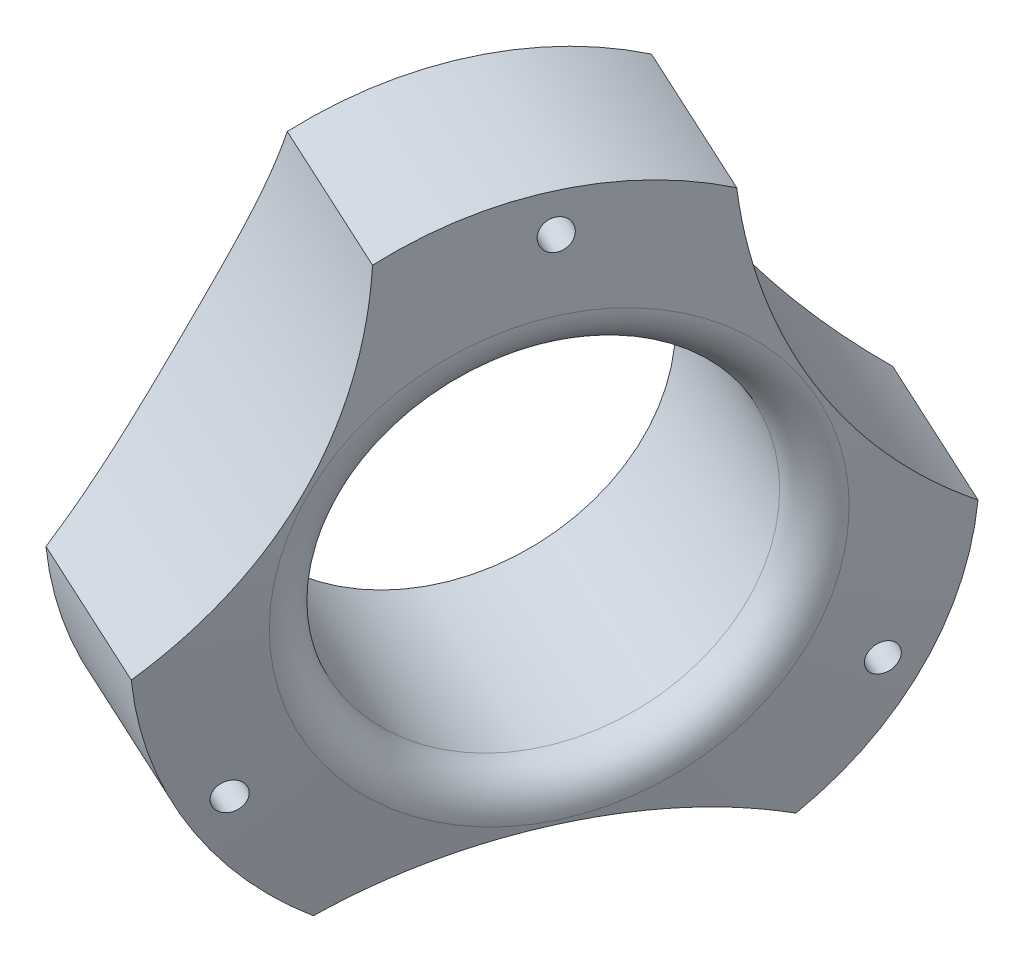
SolidWorks part; units mm, degrees
material "ABS"
ref_plane "前视基准面" through (0, 0, 0) normal (0, 0, 1) x (1, 0, 0)
ref_plane "上视基准面" through (0, 0, 0) normal (0, 1, 0) x (1, 0, 0)
ref_plane "右视基准面" through (0, 0, 0) normal (1, 0, 0) x (0, 0, -1)
other "Configuration Table"
sketch "草图1" plane through (0, 0, 0) normal (0, 1, 0) x (1, 0, 0)
  line L0 (0, 0) -> (50000, 0) construction
  line L1 (0, 0) -> (43301.2702, 25000) construction
  line L2 (0, 0) -> (25000, 43301.2702) construction
  line L3 (0, 0) -> (0, 50000) construction
  line L4 (0, 0) -> (-25000, 43301.2702) construction
  line L5 (0, 0) -> (-43301.2702, 25000) construction
  line L6 (11.039, 19.1201) -> (22.2401, 38.5209)
  line L7 (22.2401, 38.5209) -> (0, 48.7842)
  line L8 (0, 48.7842) -> (0, 24.2143)
  line L9 (0, 24.2143) -> (11.039, 19.1201)
  line L10 (13.3185, 42.638) -> (9.1284, 33.5582) construction
  line L11 (9.1284, 33.5582) -> (17.2192, 29.8245)
  line L12 (9.1284, 33.5582) -> (0, 37.7707)
  spline S0 degree 4 poles (4.5441, -13.9852) (5.069, -13.9115) (6.1117, -13.7144) (7.5966, -13.2868) (9.4525, -12.4738) (11.1485, -11.4611) (12.673, -10.2854) (14.0902, -8.9027) (15.2006, -7.528) (16.0517, -6.2294) (16.6357, -5.1571) (16.9969, -4.4036) (17.2795, -3.7437) (17.4701, -3.2541) (17.647, -2.7595) (17.7869, -2.3315) (17.8956, -1.9726) (17.9965, -1.6106) (18.0724, -1.3201) (18.1431, -1.0312) (18.201, -0.7763) (18.2495, -0.5466) (18.2961, -0.3139) (18.338, -0.0934) (18.3688, 0.0809) (18.404, 0.2961) (18.438, 0.517) (18.4698, 0.7375) (18.5019, 0.9839) (18.5336, 1.2626) (18.5616, 1.5443) (18.5855, 1.8273) (18.6051, 2.1103) (18.6204, 2.3933) (18.6344, 2.7473) (18.6427, 3.1726) (18.6402, 3.6687) (18.606, 4.6606) (18.4743, 6.0736) (18.1443, 7.891) (17.4882, 10.0676) (16.5951, 12.1579) (15.4804, 14.1385) (14.1536, 15.9992) (12.6297, 17.7192) (10.7951, 19.3989) (8.6272, 20.9716) (6.1287, 22.3558) (3.3088, 23.4722) (0.3713, 24.2251) (-2.6362, 24.611) (-5.6679, 24.6319) (-8.6804, 24.2953) (-11.6337, 23.6131) (-14.4905, 22.6011) (-17.8988, 20.9477) (-21.6682, 18.3857) (-25.4815, 14.66) (-28.8831, 9.6089) (-31.2279, 3.9916) (-32.5355, -2.3024) (-32.5832, -9.4982) (-30.886, -17.2942) (-27.0418, -25.1548) (-21.1423, -32.1629) (-13.78, -37.6027) (-5.394, -41.2569) (3.5764, -43.0207) (12.7127, -42.8868) (21.6333, -40.9289) (30.0036, -37.2857) (37.5425, -32.1439) (44.0239, -25.7248) (49.277, -18.2707) (53.1837, -10.0336) (55.6749, -1.2666) (56.7255, 7.7843) (56.3496, 16.8863) (54.5948, 25.8236) (51.5367, 34.4007) (47.2736, 42.4454) (41.6252, 50.2164) (33.2939, 58.6988) (21.6024, 66.7973) (6.2316, 72.9489) (-11.9297, 75.3897) (-30.1426, 73.5037) (-47.4501, 67.5662) (-63.0493, 58.0235) (-76.3038, 45.4399) (-86.7456, 30.4509) (-94.067, 13.7235) (-98.1075, -4.0757) (-98.837, -22.3066) (-96.337, -40.374) (-90.7813, -57.7411) (-82.4178, -73.9383) (-71.5503, -88.568) (-58.5225, -101.306) (-43.7037, -111.9004) (-27.476, -120.169) (-10.2235, -125.9948) (7.6766, -129.3207) (25.8616, -130.1437) (43.989, -128.5088) (59.522, -125.003) (72.4202, -120.5917) (82.8104, -116.0253) (90.8771, -111.8583) (98.6697, -107.1992) (106.1617, -102.071) (114.2246, -95.801) (122.6763, -88.2215) (131.2888, -79.1727) (139.0767, -69.4058) (144.8157, -60.9536) (149.48, -53.1674) (153.2371, -46.1706) (156.1751, -40.0285) (158.8259, -33.7588) (160.8418, -28.4575) (162.3378, -24.1741) (163.5443, -20.3917) (164.5049, -17.1274) (165.2564, -14.393) (165.828, -12.1982) (166.3703, -9.9944) (166.8184, -8.0627) (167.1848, -6.398) (167.4765, -5.0161) (167.7053, -3.8925) (167.892, -2.9476) (168.0629, -2.0497) (168.1956, -1.3461) (168.4043, -0.1916) (168.4882, 0.2863) (168.6688, 1.3366) (168.7622, 1.9047) (168.8711, 2.5704) (169.0198, 3.5044) (169.1948, 4.6573) (169.389, 6.0027) (169.5701, 7.3351) (169.7422, 8.6768) (169.9433, 10.3507) (170.1641, 12.3645) (170.391, 14.7154) (170.6086, 17.4069) (170.7844, 20.1009) (170.9186, 22.7976) (171.0111, 25.4959) (171.0621, 28.1953) (171.0718, 30.8952) (171.0401, 33.595) (170.9491, 36.9686) (170.6302, 43.7113) (169.6923, 53.7988) (167.722, 65.8035) (165.138, 76.2991) (163.208, 82.7681) (162.3863, 85.3399) knots 0 0 0 0 0 0.002183 0.004365 0.006343 0.00832 0.010298 0.012275 0.014479 0.01558 0.016682 0.0173 0.017918 0.018536 0.018845 0.019463 0.019772 0.020081 0.02039 0.020699 0.021008 0.021162 0.021317 0.021626 0.021918 0.022064 0.02221 0.022501 0.022793 0.023085 0.023377 0.023669 0.023961 0.024253 0.024544 0.025128 0.025712 0.026296 0.028631 0.030966 0.033302 0.035637 0.037972 0.040307 0.042695 0.045083 0.048197 0.05131 0.054424 0.057538 0.060652 0.063766 0.066879 0.069993 0.073107 0.07622 0.082448 0.088676 0.094903 0.10113 0.107357 0.114993 0.124334 0.133675 0.143016 0.152357 0.161699 0.17104 0.18038 0.189722 0.199063 0.208404 0.217745 0.227086 0.236427 0.245769 0.25511 0.264451 0.273792 0.283133 0.292474 0.301815 0.313225 0.331907 0.35059 0.369272 0.387954 0.406636 0.425318 0.444001 0.462683 0.481365 0.500047 0.518729 0.537412 0.556094 0.574776 0.593458 0.612141 0.630823 0.649505 0.668187 0.68687 0.705552 0.724234 0.742916 0.752258 0.761599 0.77094 0.780281 0.789622 0.798963 0.812975 0.826987 0.840998 0.85034 0.85501 0.864351 0.873692 0.878363 0.883033 0.887704 0.892374 0.89471 0.897045 0.89938 0.901716 0.904051 0.905219 0.906387 0.907554 0.908722 0.909306 0.90989 0.911057 0.912447 0.912794 0.913142 0.913837 0.915226 0.916616 0.918006 0.919396 0.920785 0.922175 0.924955 0.927734 0.930513 0.933293 0.936072 0.938852 0.941631 0.944411 0.94719 0.94997 0.955529 0.972205 0.988882 1 1 1 1 1 construction
  spline S1 degree 4 poles (18.3541, 0) (18.3651, 0.0621) (18.381, 0.1554) (18.404, 0.2961) (18.438, 0.517) (18.4698, 0.7375) (18.5019, 0.9839) (18.5336, 1.2626) (18.5616, 1.5443) (18.5855, 1.8273) (18.6051, 2.1103) (18.6204, 2.3933) (18.6344, 2.7473) (18.6427, 3.1726) (18.6402, 3.6687) (18.606, 4.6606) (18.4743, 6.0736) (18.1443, 7.891) (17.4882, 10.0676) (16.5951, 12.1579) (15.4804, 14.1385) (14.1536, 15.9992) (12.6297, 17.7192) (10.7951, 19.3989) (8.6272, 20.9716) (6.1287, 22.3558) (3.3088, 23.4722) (0.3713, 24.2251) (-2.6362, 24.611) (-5.6679, 24.6319) (-8.6804, 24.2953) (-11.6337, 23.6131) (-14.4905, 22.6011) (-17.8988, 20.9477) (-21.6682, 18.3857) (-25.4815, 14.66) (-28.8831, 9.6089) (-31.2279, 3.9916) (-32.5355, -2.3024) (-32.5832, -9.4982) (-30.886, -17.2942) (-27.0418, -25.1548) (-21.1423, -32.1629) (-13.78, -37.6027) (-5.394, -41.2569) (3.5764, -43.0207) (12.7127, -42.8868) (21.6333, -40.9289) (30.0036, -37.2857) (37.5425, -32.1439) (44.0239, -25.7248) (49.277, -18.2707) (53.1837, -10.0336) (55.6749, -1.2666) (56.7255, 7.7843) (56.3496, 16.8863) (54.5948, 25.8236) (51.5367, 34.4007) (47.2736, 42.4454) (41.6252, 50.2164) (33.2939, 58.6988) (21.6024, 66.7973) (6.2316, 72.9489) (-11.9297, 75.3897) (-30.1426, 73.5037) (-47.4501, 67.5662) (-63.0493, 58.0235) (-76.3038, 45.4399) (-86.7456, 30.4509) (-94.067, 13.7235) (-98.1075, -4.0757) (-98.837, -22.3066) (-96.337, -40.374) (-90.7813, -57.7411) (-82.4178, -73.9383) (-71.5503, -88.568) (-58.5225, -101.306) (-43.7037, -111.9004) (-27.476, -120.169) (-10.2235, -125.9948) (7.6766, -129.3207) (25.8616, -130.1437) (43.989, -128.5088) (59.522, -125.003) (72.4202, -120.5917) (82.8104, -116.0253) (90.8771, -111.8583) (98.6697, -107.1992) (106.1617, -102.071) (114.2246, -95.801) (122.6763, -88.2215) (131.2888, -79.1727) (139.0767, -69.4058) (144.8157, -60.9536) (149.48, -53.1674) (153.2371, -46.1706) (156.1751, -40.0285) (158.8259, -33.7588) (160.8418, -28.4575) (162.3378, -24.1741) (163.5443, -20.3917) (164.5049, -17.1274) (165.2564, -14.393) (165.828, -12.1982) (166.3703, -9.9944) (166.8184, -8.0627) (167.1848, -6.398) (167.4765, -5.0161) (167.7053, -3.8925) (167.892, -2.9476) (168.0629, -2.0497) (168.1956, -1.3461) (168.3264, -0.6223) (168.3933, -0.2484) (168.4372, 0) knots 0.021626 0.021626 0.021626 0.021626 0.021626 0.021918 0.022064 0.02221 0.022501 0.022793 0.023085 0.023377 0.023669 0.023961 0.024253 0.024544 0.025128 0.025712 0.026296 0.028631 0.030966 0.033302 0.035637 0.037972 0.040307 0.042695 0.045083 0.048197 0.05131 0.054424 0.057538 0.060652 0.063766 0.066879 0.069993 0.073107 0.07622 0.082448 0.088676 0.094903 0.10113 0.107357 0.114993 0.124334 0.133675 0.143016 0.152357 0.161699 0.17104 0.18038 0.189722 0.199063 0.208404 0.217745 0.227086 0.236427 0.245769 0.25511 0.264451 0.273792 0.283133 0.292474 0.301815 0.313225 0.331907 0.35059 0.369272 0.387954 0.406636 0.425318 0.444001 0.462683 0.481365 0.500047 0.518729 0.537412 0.556094 0.574776 0.593458 0.612141 0.630823 0.649505 0.668187 0.68687 0.705552 0.724234 0.742916 0.752258 0.761599 0.77094 0.780281 0.789622 0.798963 0.812975 0.826987 0.840998 0.85034 0.85501 0.864351 0.873692 0.878363 0.883033 0.887704 0.892374 0.89471 0.897045 0.89938 0.901716 0.904051 0.905219 0.906387 0.907554 0.908722 0.909306 0.90989 0.911057 0.911057 0.911057 0.911057 0.911057
  spline S2 degree 4 poles (26.7771, -19.4547) (27.2791, -18.9699) (28.2564, -17.9726) (29.6389, -16.3972) (31.5138, -13.8737) (32.9647, -11.4834) (34.0651, -9.2997) (34.8847, -7.3726) (35.3191, -6.2309) (35.6599, -5.2409) (35.9229, -4.4091) (36.0959, -3.8235) (36.2363, -3.3192) (36.3702, -2.8132) (36.4765, -2.3905) (36.5777, -1.9654) (36.6735, -1.5395) (36.7371, -1.2443) (36.7899, -0.9895) (36.8338, -0.7701) (36.8689, -0.5895) (36.9122, -0.3614) (36.9643, -0.079) (37.0022, 0.137) (37.056, 0.4587) (37.1012, 0.7414) (37.1347, 0.96) (37.1737, 1.2255) (37.2176, 1.5413) (37.2661, 1.9157) (37.3168, 2.3441) (37.3624, 2.7721) (37.4134, 3.3079) (37.4649, 3.9519) (37.524, 4.9191) (37.5642, 6.2107) (37.5499, 8.58) (37.2749, 12.0191) (36.4953, 16.2666) (34.9181, 21.2024) (32.7382, 25.9024) (30.2297, 29.9345) (27.5748, 33.3344) (24.3272, 36.7897) (20.4102, 40.1789) (15.3713, 43.5302) (9.113, 46.471) (2.4988, 48.4837) (-3.4771, 49.4179) (-8.6498, 49.6296) (-15.5372, 49.2939) (-22.3494, 48.0444) (-29.7217, 45.4984) (-37.3047, 41.3681) (-42.9225, 37.3494) (-49.2948, 31.5248) (-55.7813, 23.4083) (-61.4472, 12.6507) (-65.4181, -1.9048) (-66.0143, -20.496) (-61.2011, -38.6277) (-51.6663, -54.6681) (-39.5267, -67.0168) (-28.241, -75.0457) (-15.7631, -81.0448) (-2.4709, -84.9081) (11.2641, -86.5959) (25.0917, -86.1269) (38.6859, -83.5703) (51.7521, -79.0376) (62.4941, -73.4702) (71.0671, -67.6624) (77.7289, -62.1925) (82.7475, -57.4634) (87.4361, -52.4071) (91.7776, -47.05) (95.7571, -41.4188) (99.3618, -35.5409) (102.1786, -30.2056) (104.3465, -25.5122) (105.8226, -21.9278) (106.7439, -19.5134) (107.4694, -17.486) (108.0246, -15.8552) (108.5543, -14.216) (109.0585, -12.5687) (109.5372, -10.914) (109.9904, -9.2519) (110.418, -7.5833) (110.7697, -6.1172) (111.0551, -4.8577) (111.2824, -3.8044) (111.4574, -2.9629) (111.6056, -2.2213) (111.7181, -1.6396) (111.7961, -1.2276) (111.8764, -0.7956) (111.9824, -0.2107) (112.0406, 0.1173) (112.149, 0.7476) (112.2197, 1.1704) (112.2736, 1.499) (112.3401, 1.912) (112.4454, 2.5814) (112.5829, 3.4978) (112.7468, 4.6683) (112.9181, 6.007) (113.1127, 7.6834) (113.3147, 9.6981) (113.5046, 12.0531) (113.6588, 14.7487) (113.7504, 17.4473) (113.7796, 20.1472) (113.7303, 24.197) (113.4243, 30.2662) (112.8255, 35.6383) (112.057, 40.3021) (111.5392, 42.9519) knots 0 0 0 0 0 0.005611 0.011222 0.016833 0.02525 0.028055 0.030861 0.033666 0.035069 0.036472 0.037875 0.038576 0.039277 0.04068 0.041381 0.042083 0.042784 0.043135 0.043486 0.043836 0.044187 0.044888 0.045754 0.046187 0.04662 0.047052 0.047485 0.048351 0.049216 0.050082 0.050948 0.051813 0.053545 0.055276 0.058738 0.062201 0.072588 0.082976 0.093363 0.103751 0.114138 0.121063 0.127988 0.141838 0.155688 0.169538 0.183388 0.197238 0.204163 0.211088 0.238788 0.252638 0.266488 0.280339 0.294189 0.321888 0.349589 0.377289 0.414571 0.469971 0.497671 0.525371 0.553071 0.580771 0.608471 0.636171 0.663871 0.691571 0.719271 0.746971 0.760821 0.774671 0.788521 0.802371 0.816222 0.830072 0.843922 0.857772 0.864697 0.871622 0.875084 0.878547 0.882009 0.885472 0.888934 0.892397 0.895859 0.899322 0.902784 0.904515 0.906247 0.907978 0.909709 0.910575 0.911008 0.91144 0.913172 0.914528 0.915207 0.915885 0.916563 0.917242 0.918599 0.921312 0.924025 0.926739 0.929452 0.934879 0.940306 0.945732 0.951159 0.956586 0.962013 0.978293 1 1 1 1 1 construction
  spline S3 degree 4 poles (36.9778, 0) (36.994, 0.0921) (37.0177, 0.2297) (37.056, 0.4587) (37.1012, 0.7414) (37.1347, 0.96) (37.1737, 1.2255) (37.2176, 1.5413) (37.2661, 1.9157) (37.3168, 2.3441) (37.3624, 2.7721) (37.4134, 3.3079) (37.4649, 3.9519) (37.524, 4.9191) (37.5642, 6.2107) (37.5499, 8.58) (37.2749, 12.0191) (36.4953, 16.2666) (34.9181, 21.2024) (32.7382, 25.9024) (30.2297, 29.9345) (27.5748, 33.3344) (24.3272, 36.7897) (20.4102, 40.1789) (15.3713, 43.5302) (9.113, 46.471) (2.4988, 48.4837) (-3.4771, 49.4179) (-8.6498, 49.6296) (-15.5372, 49.2939) (-22.3494, 48.0444) (-29.7217, 45.4984) (-37.3047, 41.3681) (-42.9225, 37.3494) (-49.2948, 31.5248) (-55.7813, 23.4083) (-61.4472, 12.6507) (-65.4181, -1.9048) (-66.0143, -20.496) (-61.2011, -38.6277) (-51.6663, -54.6681) (-39.5267, -67.0168) (-28.241, -75.0457) (-15.7631, -81.0448) (-2.4709, -84.9081) (11.2641, -86.5959) (25.0917, -86.1269) (38.6859, -83.5703) (51.7521, -79.0376) (62.4941, -73.4702) (71.0671, -67.6624) (77.7289, -62.1925) (82.7475, -57.4634) (87.4361, -52.4071) (91.7776, -47.05) (95.7571, -41.4188) (99.3618, -35.5409) (102.1786, -30.2056) (104.3465, -25.5122) (105.8226, -21.9278) (106.7439, -19.5134) (107.4694, -17.486) (108.0246, -15.8552) (108.5543, -14.216) (109.0585, -12.5687) (109.5372, -10.914) (109.9904, -9.2519) (110.418, -7.5833) (110.7697, -6.1172) (111.0551, -4.8577) (111.2824, -3.8044) (111.4574, -2.9629) (111.6056, -2.2213) (111.7181, -1.6396) (111.7961, -1.2276) (111.8764, -0.7956) (111.946, -0.4114) (111.9868, -0.1841) (112.0193, 0) knots 0.044888 0.044888 0.044888 0.044888 0.044888 0.045754 0.046187 0.04662 0.047052 0.047485 0.048351 0.049216 0.050082 0.050948 0.051813 0.053545 0.055276 0.058738 0.062201 0.072588 0.082976 0.093363 0.103751 0.114138 0.121063 0.127988 0.141838 0.155688 0.169538 0.183388 0.197238 0.204163 0.211088 0.238788 0.252638 0.266488 0.280339 0.294189 0.321888 0.349589 0.377289 0.414571 0.469971 0.497671 0.525371 0.553071 0.580771 0.608471 0.636171 0.663871 0.691571 0.719271 0.746971 0.760821 0.774671 0.788521 0.802371 0.816222 0.830072 0.843922 0.857772 0.864697 0.871622 0.875084 0.878547 0.882009 0.885472 0.888934 0.892397 0.895859 0.899322 0.902784 0.904515 0.906247 0.907978 0.909709 0.910575 0.911008 0.91144 0.913172 0.913172 0.913172 0.913172 0.913172
  point P28 (9.1284, 33.5582)
  dimension "D1" = 10
revolve "旋转1" add sketch "草图1" angle 360 about L7 region at (7.2301, 0, -28.3935) region at (5.6712, 0, -21.9501)
ref_plane "基准面1" through (2.8492, 0, 1.3148) normal (0.908, 0, 0.419) x (0.419, 0, -0.908)
sketch "草图2" plane through (2.8492, 0, 1.3148) normal (0.908, 0, 0.419) x (0.419, 0, -0.908)
  line L0 (44.2951, 22.309) -> (44.2951, 19.809) construction
  line L1 (44.2951, 0) -> (13.9392, 0) construction
  line L2 (44.2951, 0) -> (5.324, 22.5) construction
  circle A0 centre (44.2951, 0) radius 22.309 construction
  circle A1 centre (44.2951, 19.809) radius 1
  circle A2 centre (5.324, 22.5) radius 29.5
  circle A3 centre (83.2663, 22.5) radius 29.5
  circle A4 centre (61.4502, -9.9045) radius 1
  circle A5 centre (44.2951, -45) radius 29.5
  circle A6 centre (27.14, -9.9045) radius 1
  circle A7 centre (44.2951, 0) radius 12.5
  dimension "D2" = 2
  dimension "D4" = 59
  dimension "D6" = 25
  dimension "D1" = 2.5
  dimension "D3" = 30
  dimension "D5" = 3
extrude "切除-拉伸1" cut sketch "草图2" against normal blind 24 contours A2 | A3 | A5 | A1 | A6 | A4 | A7 region at (21.4093, 19.809, -38.9043) region at (5.08, 22.5, -3.5192) region at (37.7386, 22.5, -74.2894) region at (28.5974, -9.9045, -54.4808) region at (21.4093, -45, -38.9043) region at (14.2211, -9.9045, -23.3278) region at (21.4093, 0, -38.9043)
fillet "圆角1" radius 2.5 1 edges at (15.964, 0, -27.6504)
ref_point "点1"
ref_plane "基准面2" through (-13.3225, 0, -6.148) normal (-0.908, 0, -0.419) x (-0.419, 0, 0.908)
